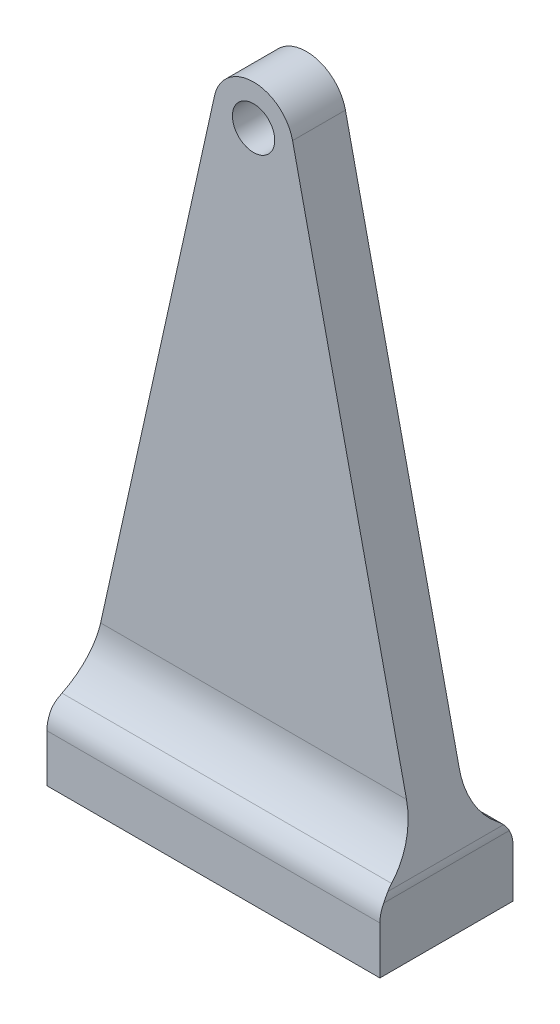
SolidWorks part; units mm, degrees
ref_plane "Front Plane" through (0, 0, 0) normal (0, 0, 1) x (1, 0, 0)
ref_plane "Top Plane" through (0, 0, 0) normal (0, 1, 0) x (1, 0, 0)
ref_plane "Right Plane" through (0, 0, 0) normal (1, 0, 0) x (0, 0, -1)
sketch "Sketch1" plane through (0, 0, 0) normal (0, 0, 1) x (1, 0, 0)
  line L0 (-5.8576, 86.2993) -> (-25, 0)
  line L1 (5.8576, 86.2993) -> (25, 0)
  line L5 (-25, 0) -> (-25, -10)
  line L6 (-25, -10) -> (25, -10)
  line L7 (25, 0) -> (25, -10)
  circle A0 centre (0, 85) radius 3.175
  arc A1 (5.8576, 86.2993) -> (-5.8576, 86.2993) centre (0, 85) ccw
  point P10 (0, -10)
  dimension "D1" = 6.35
  dimension "D2" = 12
  dimension "D3" = 50
  dimension "D5" = 10
  dimension "D4" = 95
extrude "Boss-Extrude1" add sketch "Sketch1" along normal blind 20
sketch "Sketch2" plane through (0, 0, 0) normal (1, 0, 0) x (0, 0, -1)
  line L0 (-20, 0) -> (-13.9688, 0)
  line L1 (-13.9688, 0) -> (-13.9688, 91)
  line L2 (0, 91) -> (-20, 91) construction
  line L3 (-13.9688, 91) -> (-20, 91)
  line L4 (-20, 91) -> (-20, 0)
  line L5 (0, 0) -> (0, 91)
  line L6 (0, 91) -> (-6.0312, 91)
  line L7 (-6.0312, 91) -> (-6.0312, 0)
  line L8 (-6.0312, 0) -> (0, 0)
  line L12 (-20, 0) -> (0, 0) construction
  dimension "D1" = 7.9375
extrude "Cut-Extrude1" cut sketch "Sketch2" along normal up to vertex (25 mm away) and the other way up to vertex (25 mm away) up to point (25, 0, 20) other way up to point (-25, 0, 20)
fillet "Fillet1" radius 10 2 edges at (0, 0, 6.0312) (0, 0, 13.9688)
fillet "Fillet2" radius 5 4 edges at (-25, 0, 10) (25, 0, 10) (0, 0, 0) (0, 0, 20)
sketch "Sketch3" plane through (0, -10, 0) normal (0, -1, 0) x (1, 0, 0)
  line L0 (-25.5, 20.5) -> (25.5, 20.5) construction
  line L2 (-25.5, -0.5) -> (-25.5, 20.5) construction
  line L3 (25.5, -0.5) -> (-25.5, -0.5) construction
  line L7 (25.5, 20.5) -> (25.5, -0.5) construction
  circle A0 centre (-15.5, 14.5) radius 2.3813
  circle A1 centre (-15.5, 5.5) radius 2.3813
  circle A2 centre (0, 5.5) radius 2.3813 construction
  circle A3 centre (0, 14.5) radius 2.3813 construction
  circle A4 centre (15.5, 14.5) radius 2.3813
  circle A5 centre (15.5, 5.5) radius 2.3813
  dimension "D1" = 4.7625
  dimension "D2" = 6
  dimension "D3" = 10
  dimension "D5" = 6
extrude "Cut-Extrude2" cut sketch "Sketch3" against normal blind 6.4
equation "\"tower_height\"=95"
equation "\"bearing_slot_diameter\"=20"
equation "\"D1@Boss-Extrude1\"=\"bearing_slot_diameter\""
equation "\"D4@Sketch1\"=\"tower_height\""
equation "\"insert_drill_diameter\"=4.7625"
equation "\"D1@Sketch3\"=\"insert_drill_diameter\""
equation "\"insert_drill_depth\"=6.4"
equation "\"D1@Cut-Extrude2\"=\"insert_drill_depth\""
equation "\"D5@Sketch3\"=\"D2@Sketch3\""
equation "\"D4@Sketch3\"=\"D3@Sketch3\""
